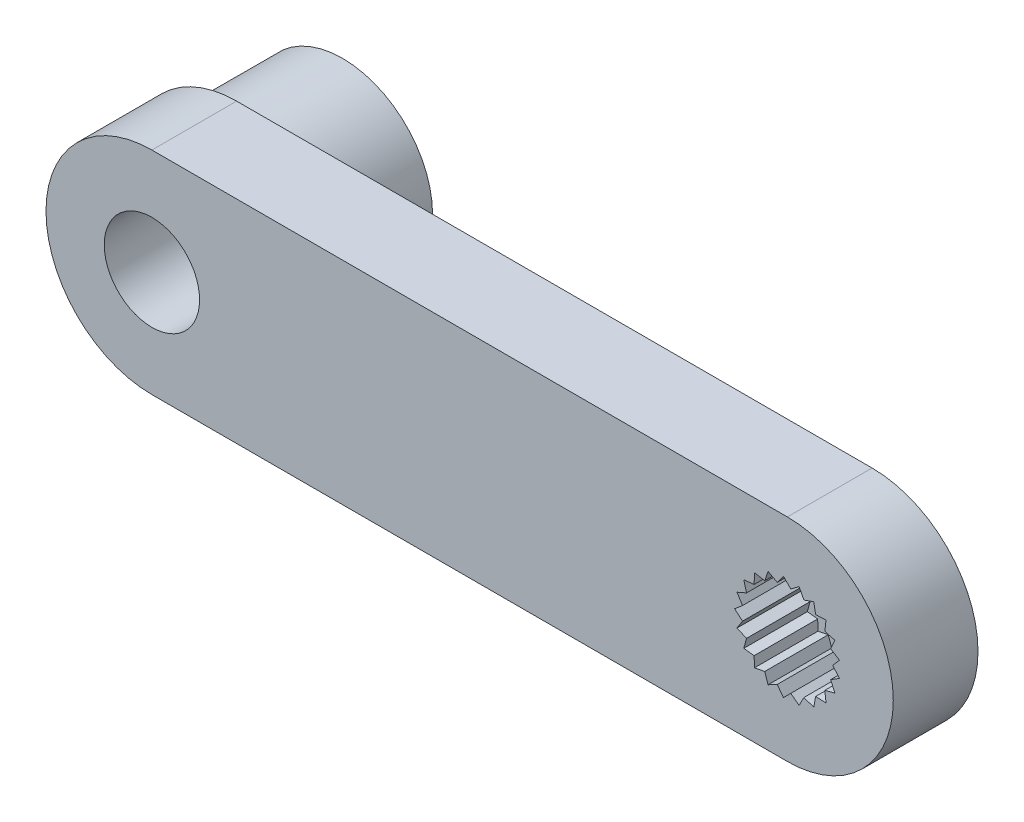
SolidWorks part; units mm, degrees
ref_plane "Front Plane" through (0, 0, 0) normal (0, 0, 1) x (1, 0, 0)
ref_plane "Top Plane" through (0, 0, 0) normal (0, 1, 0) x (1, 0, 0)
ref_plane "Right Plane" through (0, 0, 0) normal (1, 0, 0) x (0, 0, -1)
sketch "Sketch1" plane through (0, 0, 0) normal (0, 0, 1) x (1, 0, 0)
  line L0 (0, 0) -> (30, 0) construction
  line L1 (0, 5) -> (30, 5)
  line L2 (0, -5) -> (30, -5)
  arc A0 (0, 5) -> (0, -5) centre (0, 0) ccw
  arc A1 (30, -5) -> (30, 5) centre (30, 0) ccw
  circle A2 centre (0, 0) radius 2.25
  circle A4 centre (30, 0) radius 1
  point P3 (15, 0)
  point P12 (0, 0)
  dimension "D1" = 5
  dimension "D3" = 4.5
  dimension "D4" = 2
  dimension "D2" = 30
extrude "Boss-Extrude1" add sketch "Sketch1" along normal mid plane 4
sketch "Sketch2" plane through (0, 0, 2) normal (0, 0, 1) x (1, 0, 0)
  circle A0 centre (30, 0) radius 2.49
  circle A1 centre (30, 0) radius 1 construction
  point P2 (27, -1.6708)
  dimension "D1" = 4.98
extrude "Cut-Extrude1" cut sketch "Sketch2" against normal blind 3
sketch "Sketch3" plane through (0, 0, -2) normal (0, 0, -1) x (-1, 0, 0)
  circle A2 centre (-30, 0) radius 3
  circle A4 centre (-30, 0) radius 1 construction
  circle A5 centre (-30, 0) radius 1
  point P2 (-25.9351, -0.1952)
  dimension "D1" = 6
extrude "Boss-Extrude2" add sketch "Sketch3" along normal blind 1
sketch "Sketch4" plane through (0, 0, -2) normal (0, 0, -1) x (-1, 0, 0)
  circle A0 centre (0, 0) radius 2.25 construction
  circle A1 centre (0, 0) radius 2.25
  circle A2 centre (0, 0) radius 4.25
  dimension "D1" = 2
extrude "Boss-Extrude3" add sketch "Sketch4" along normal blind 5
sketch "Sketch5" plane through (0, 0, 2) normal (0, 0, 1) x (1, 0, 0)
  line L0 (30, 0) -> (32.49, 0) construction
  line L3 (30, 0) -> (32.4622, 0.3711) construction
  line L4 (32.4622, 0.3711) -> (32.14, 0)
  line L5 (32.14, 0) -> (32.4622, -0.3711)
  circle A0 centre (30, 0) radius 2.49 construction
  arc A1 (32.4622, -0.3711) -> (32.4622, 0.3711) centre (30, 0) ccw
  point P3 (32.4622, -0.3711)
  point P7 (0, 0)
  dimension "D1" = 8.571
  dimension "D2" = 0.35
extrude "Boss-Extrude4" add sketch "Sketch5" against normal blind 3.2
pattern_circular "CirPattern2" count 21 over 360 about axis through (30, 0, -1) along (0, 0, 1) of "Boss-Extrude4" reverse direction yes
